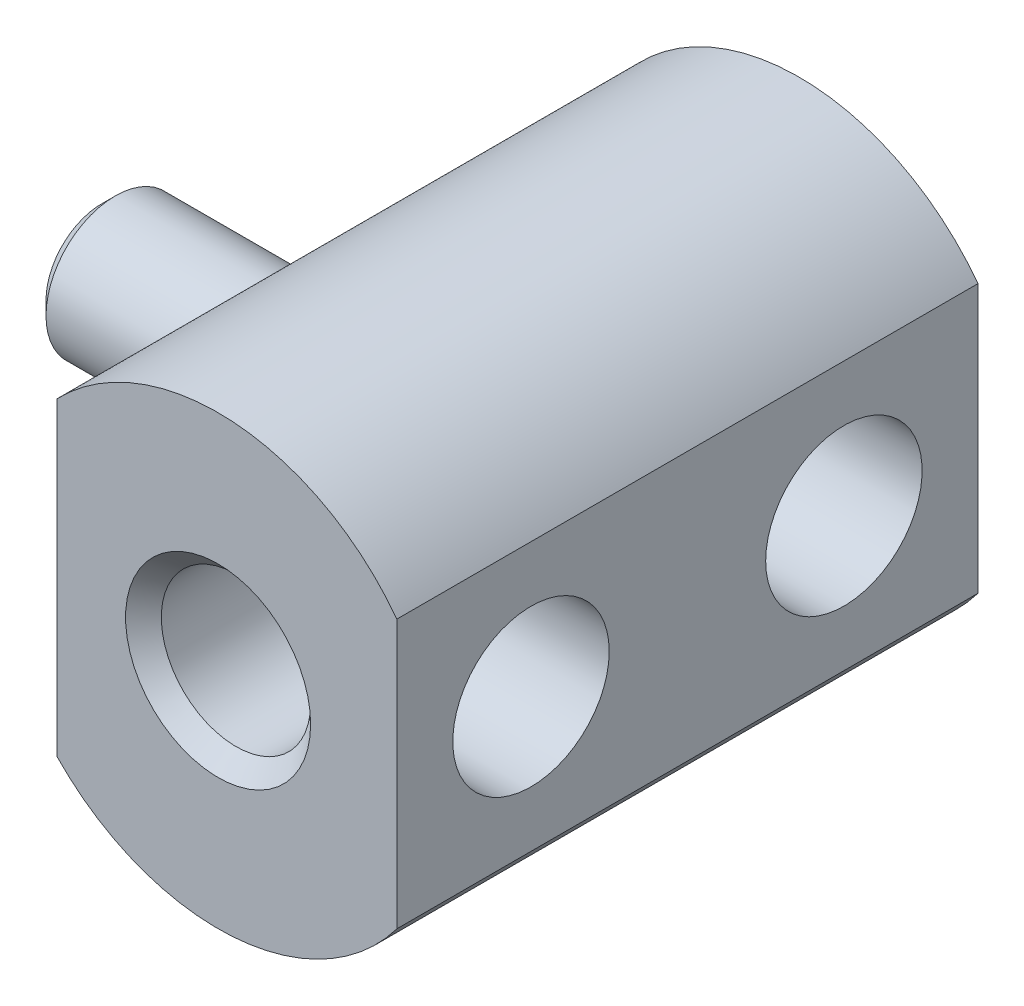
SolidWorks part; units mm, degrees
material "PLA2"
ref_plane "Front Plane" through (0, 0, 0) normal (0, 0, 1) x (1, 0, 0)
ref_plane "Top Plane" through (0, 0, 0) normal (0, 1, 0) x (1, 0, 0)
ref_plane "Right Plane" through (0, 0, 0) normal (1, 0, 0) x (0, 0, -1)
sketch "Sketch1" plane through (0, 0, 0) normal (0, 0, 1) x (1, 0, 0)
  circle A0 centre (0, 0) radius 2.1209
  circle A1 centre (0, 0) radius 6.35
  dimension "D1" = 4.2418
  dimension "D2" = 12.7
extrude "Boss-Extrude1" add sketch "Sketch1" along normal mid plane 16.51
sketch "Sketch3" plane through (0, 0, 8.255) normal (0, 0, 1) x (1, 0, 0)
  line L0 (-4.572, 4.4067) -> (-4.572, -4.4067)
  line L1 (0, 0.0885) -> (0, 50000.0885) construction
  line L3 (5.08, 3.81) -> (5.08, -3.81)
  line L4 (5.08, 0) -> (6.35, 0) construction
  arc A0 (-4.572, 4.4067) -> (-4.572, -4.4067) centre (0, 0) ccw
  arc A2 (5.08, -3.81) -> (5.08, 3.81) centre (0, 0) ccw
  circle A3 centre (0, 0) radius 6.35 construction
  point P1 (-6.35, 0)
  dimension "D1" = 1.778
  dimension "D2" = 1.27
extrude "Cut-Extrude1" cut sketch "Sketch3" against normal through all
sketch "Sketch4" plane through (-4.572, 0, 0) normal (-1, 0, 0) x (0, 0, 1)
  circle A0 centre (0, 0) radius 1.9685
  dimension "D1" = 3.937
extrude "Boss-Extrude2" add sketch "Sketch4" along normal blind 6.985
fillet "Fillet1" radius 1.27 1 edges at (-4.572, 0, 1.9685)
chamfer "Chamfer1" distance 0.381 angle 45 1 edges at (-11.557, 0, 1.9685)
sketch "Sketch5" plane through (5.08, 0, 0) normal (1, 0, 0) x (0, 0, -1)
  line L0 (0, 0) -> (0, 50000) construction
  line L1 (-4.445, 0) -> (0, 0) construction
  circle A0 centre (-4.445, 0) radius 2.2225
  circle A1 centre (4.445, 0) radius 2.2225
  dimension "D1" = 4.445
  dimension "D2" = 8.89
extrude "Cut-Extrude2" cut sketch "Sketch5" against normal blind 4.445
chamfer "Chamfer2" distance 0.508 angle 45 2 edges at (2.1209, 0, -8.255) (2.1209, 0, 8.255)
